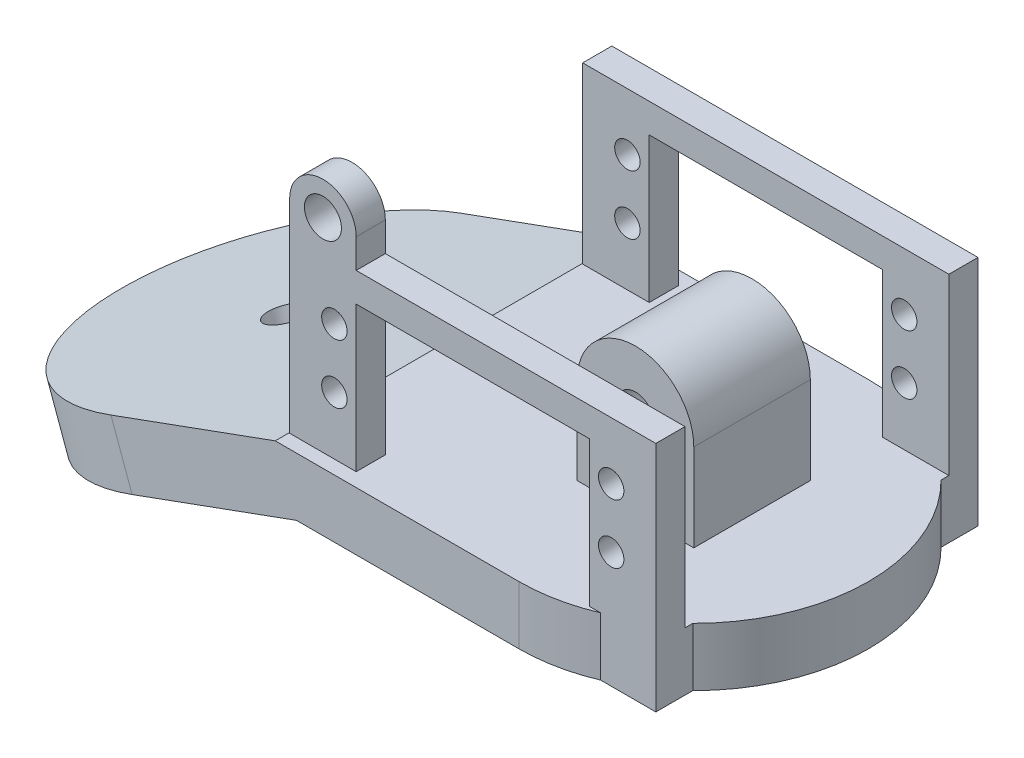
SolidWorks part; units mm, degrees
ref_plane "Plan de face" through (0, 0, 0) normal (0, 0, 1) x (1, 0, 0)
ref_plane "Plan de dessus" through (0, 0, 0) normal (0, 1, 0) x (1, 0, 0)
ref_plane "Plan de droite" through (0, 0, 0) normal (1, 0, 0) x (0, 0, -1)
sketch "Esquisse5" plane through (0, 0, 0) normal (0, 1, 0) x (1, 0, 0)
  line L0 (40, 0) -> (-40, 0) construction
  line L1 (40, -30) -> (-40, -30)
  line L2 (40, 30) -> (-40, 30)
  arc A0 (40, -30) -> (40, 30) centre (40, 0) ccw
  arc A1 (-40, 30) -> (-40, -30) centre (-40, 0) ccw
  point P2 (0, 0)
  dimension "D2" = 30
  dimension "D1" = 80
extrude "Boss.-Extru.3" add sketch "Esquisse5" along normal mid plane 10
sketch "Esquisse36" plane through (0, 0, 0) normal (0, 0, 1) x (1, 0, 0)
  line L0 (0, 0) -> (9.0993, -25)
  line L1 (9.0993, -25) -> (-110, -25)
  line L2 (-110, -25) -> (-110, 35)
  line L3 (-110, 35) -> (-12.739, 35)
  line L4 (-12.739, 35) -> (0, 0)
  line L5 (40, -5) -> (-40, -5) construction
  line L6 (40, 5) -> (-40, 5) construction
  line L7 (-40, 5) -> (-40, -5) construction
  dimension "D1" = 180
  dimension "D2" = 20
  dimension "D3" = 70
  dimension "D4" = 30
  dimension "D5" = 70
sketch "Esquisse7" plane through (0, 0, 0) normal (0, 0, 1) x (1, 0, 0)
  line L0 (40, 5) -> (30, 5)
  line L1 (-40, 5) -> (40, 5) construction
  line L2 (30, 5) -> (30, 20)
  line L3 (30, 20) -> (50, 20)
  line L4 (50, 20) -> (50, 5)
  line L5 (70, 5) -> (40, 5) construction
  line L6 (50, 5) -> (40, 5)
  arc A0 (30, 20) -> (50, 20) centre (40, 20) cw
  circle A1 centre (40, 20) radius 3.175
  dimension "D1" = 10
  dimension "D3" = 6.35
  dimension "D2" = 15
extrude "Boss.-Extru.5" add sketch "Esquisse7" along normal mid plane 20 contours A1 L3 A0 | A1 L3 L2 L0 L6 L4 region at (40, 12.1572, 0) region at (40, 24.5689, 0)
sketch "Esquisse10" plane through (0, -5, 0) normal (0, -1, 0) x (1, 0, 0)
  point P0 (40, 0)
ref_plane "Plan1" through (0, 0, 22.64) normal (0, 0, 1) x (1, 0, 0)
sketch "Esquisse13" plane through (0, 0, 22.64) normal (0, 0, 1) x (1, 0, 0)
  line L0 (-40, 5) -> (40, 5) construction
  line L1 (3.3, 5) -> (56.13, 5)
  line L2 (3.3, 5) -> (3.3, 29.91) construction
  line L3 (3.3, 29.91) -> (56.13, 29.91) construction
  line L4 (56.13, 5) -> (56.13, 29.91) construction
  line L5 (3.3, 5) -> (-1.7, 5)
  line L6 (-1.7, 5) -> (-1.7, 34.91)
  line L7 (-1.7, 34.91) -> (61.13, 34.91)
  line L8 (61.13, 34.91) -> (61.13, 5)
  line L9 (61.13, 5) -> (56.13, 5)
  line L10 (61.13, 5) -> (56.13, 5)
  line L11 (-1.7, 5) -> (3.3, 5)
  line L12 (9.715, 5) -> (9.715, 29.91)
  line L13 (9.715, 29.91) -> (49.715, 29.91)
  line L14 (49.715, 29.91) -> (49.715, 5)
  line L15 (49.715, 5) -> (9.715, 5)
  circle A0 centre (40, 20) radius 3.175 construction
  circle A2 centre (53.47, 25.08) radius 2.18
  circle A3 centre (53.47, 14.92) radius 2.18
  circle A4 centre (5.97, 25.08) radius 2.18
  circle A5 centre (5.97, 14.92) radius 2.18
  point P6 (56.13, 17.455)
  point P24 (29.715, 29.91)
  point P26 (29.715, 34.91)
  dimension "D4" = 5
  dimension "D7" = 4.36
  dimension "D8" = 47.5
  dimension "D12" = 10.16
  dimension "D1" = 52.83
  dimension "D2" = 16.13
  dimension "D3" = 24.91
  dimension "D5" = 4.83
  dimension "D6" = 2.67
  dimension "D9" = 47.5
  dimension "D10" = 0
  dimension "D11" = 0
  dimension "D13" = 0
  dimension "D14" = 5
  dimension "D15" = 5
  dimension "D16" = 40
  dimension "D17" = 0
  dimension "D18" = 0
extrude "Boss.-Extru.8" add sketch "Esquisse13" along normal blind 5 contours L13 L14 L1 L9 L8 L7 L6 L5 L12 A5 A4 A3 A2 region at (0.8, 5.6959, 22.64)
mirror "Symétrie2" about plane through (0, 0, 0) normal (0, 0, 1) of "Boss.-Extru.8"
sketch "Esquisse14" plane through (0, 0, 0) normal (0, 0, 1) x (1, 0, 0)
  point P0 (40, 20)
sketch "Esquisse33" plane through (0, 5, 0) normal (0, -1, 0) x (1, 0, 0)
  line L0 (51.6632, -27.64) -> (61.13, -27.64) construction
  line L1 (61.13, 27.64) -> (51.6632, 27.64)
  line L2 (61.13, 27.64) -> (61.13, -27.64)
  line L3 (61.13, -27.64) -> (51.6632, -27.64)
  line L4 (51.6632, 27.64) -> (51.6632, -27.64)
  dimension "D1" = 0
  dimension "D2" = 0
extrude "Boss.-Extru.10" add sketch "Esquisse33" along normal up to surface (10 mm away) up to face at (0, -5, 0)
sketch "Esquisse34" plane through (0, 0, 0) normal (0, 1, 0) x (1, 0, 0)
  line L0 (0, 0) -> (0, 29.4868) construction
extrude "Enlèv. mat.-Extru.6" cut sketch "Esquisse36" against normal mid plane 130
ref_plane "Plan11" through (0, 0, 0) normal (-0.342, 0.9397, 0) x (0, 0, -1)
sketch "Esquisse35" plane through (0, 0, 0) normal (-0.342, 0.9397, 0) x (0, 0, -1)
  circle A0 centre (0, 30) radius 30
  dimension "D1" = 60
  dimension "D2" = 0
extrude "Boss.-Extru.11" add sketch "Esquisse35" along normal mid plane 10.64
sketch "Esquisse37" plane through (0, 0, 0) normal (0, 0, 1) x (1, 0, 0)
sketch "Esquisse38" plane through (-1.8195, 4.9992, 0) normal (-0.342, 0.9397, 0) x (0.9397, 0.342, 0)
  point P0 (0, 0)
  point P1 (-30, 0)
  point P4 (0, 0)
sketch "Esquisse39" plane through (1.8195, -4.9992, 0) normal (0.342, -0.9397, 0) x (0.9397, 0.342, 0)
  point P0 (-30, 0)
sketch "Esquisse40" plane through (0, 0, 0) normal (0, 0, 1) x (1, 0, 0)
  line L0 (-26.3712, -15.2598) -> (-30.0103, -5.2614)
  line L1 (-26.3712, -15.2598) -> (1.8195, -4.9992)
  line L2 (-30.0103, -5.2614) -> (-1.8195, 4.9992)
  line L3 (1.8195, -4.9992) -> (-1.8195, 4.9992)
  dimension "D1" = 0
extrude "Boss.-Extru.12" add sketch "Esquisse40" along normal mid plane 60
sketch "Esquisse41" plane through (-1.8195, 4.9992, 0) normal (-0.342, 0.9397, 0) x (0.9397, 0.342, 0)
  circle A0 centre (-30, 0) radius 3.175
  dimension "D1" = 6.35
extrude "Enlèv. mat.-Extru.7" cut sketch "Esquisse41" against normal blind 60
sketch "Esquisse42" plane through (0, 0, 27.64) normal (0, 0, 1) x (1, 0, 0)
  line L0 (-1.7, 34.91) -> (-1.7, 39.91)
  line L1 (-1.7, 39.91) -> (9.715, 39.91)
  line L2 (9.715, 39.91) -> (9.715, 34.91)
  line L3 (-1.7, 34.91) -> (61.13, 34.91) construction
  line L4 (9.715, 34.91) -> (-1.7, 34.91)
  line L5 (9.715, 5) -> (9.715, 29.91) construction
  arc A0 (-1.7, 39.91) -> (9.715, 39.91) centre (4.0075, 39.91) cw
  circle A1 centre (4.0075, 39.91) radius 3.175
  line M15 (61.13, 34.91) -> (-1.7, 34.91)
  dimension "D3" = 6.35
  dimension "D1" = 5
  dimension "D2" = 0
extrude "Boss.-Extru.13" add sketch "Esquisse42" against normal up to surface (5 mm away) contours A1 L1 A0 | A1 L1 L0 L2 M15 region at (-1.5754, 37.41, 27.64) region at (4.0075, 45.4899, 27.64) up to face at (8.15, 14.92, 22.64)
